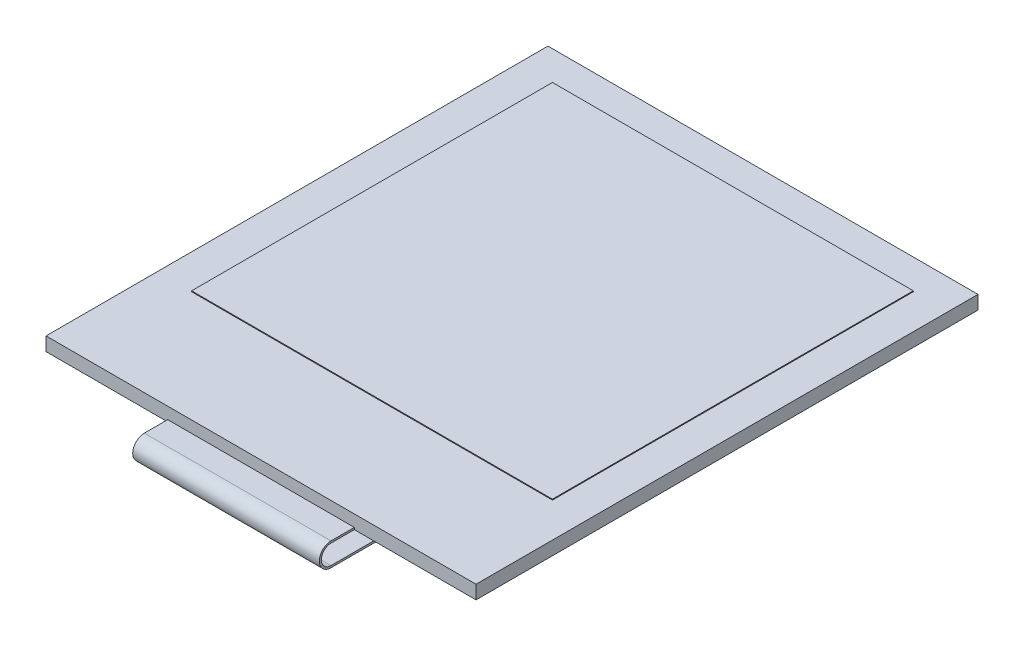
SolidWorks part; units mm, degrees
ref_plane "前视基准面" through (0, 0, 0) normal (0, 0, 1) x (1, 0, 0)
ref_plane "上视基准面" through (0, 0, 0) normal (0, 1, 0) x (1, 0, 0)
ref_plane "右视基准面" through (0, 0, 0) normal (1, 0, 0) x (0, 0, -1)
other "Configuration Table"
sketch "草图1" plane through (0, 0, 0) normal (0, 1, 0) x (1, 0, 0)
  line L1 (-9.28, -9.28) -> (9.28, -9.28)
  line L2 (-9.28, -9.28) -> (-9.28, 9.28)
  line L3 (-9.28, 9.28) -> (9.28, 9.28)
  line L4 (9.28, -9.28) -> (9.28, 9.28)
  line L5 (-9.28, -9.28) -> (9.28, 9.28) construction
  line L6 (-9.28, 9.28) -> (9.28, -9.28) construction
  line L7 (-11.06, 10.83) -> (11.06, 10.83)
  line L8 (-11.06, 10.83) -> (-11.06, -14.99)
  line L9 (-11.06, -14.99) -> (11.06, -14.99)
  line L10 (11.06, 10.83) -> (11.06, -14.99)
  point P0 (0, 0)
  dimension "D1" = 18.56
  dimension "D2" = 22.12
  dimension "D3" = 25.82
  dimension "D4" = 11.06
  dimension "D5" = 14.99
extrude "凸台-拉伸1" add sketch "草图1" along normal blind 0.7
extrude "凸台-拉伸2" add sketch "草图1<2>" along normal blind 0.745 contours L1 L4 L3 L2 region at (0, 0, 0)
sketch "草图1<2>" plane through (0, 0, 0) normal (0, 1, 0) x (1, 0, 0) same geometry as "草图1"
sketch "草图2" plane through (0, 0, 0) normal (1, 0, 0) x (0, 0, -1)
  line L0 (-14.99, 0) -> (-16.19, 0)
  line L1 (-16.19, -1) -> (-12.76, -1)
  line L2 (-16.19, 0) -> (-16.19, -1) construction
  line L3 (-14.99, 0.1) -> (-16.19, 0.1)
  line L4 (-16.19, -1.1) -> (-12.76, -1.1)
  line L5 (-14.99, 0) -> (-14.99, 0.1)
  line L6 (-12.76, -1) -> (-12.76, -1.1)
  arc A0 (-16.19, 0) -> (-16.19, -1) centre (-16.19, -0.5) ccw
  arc A1 (-16.19, 0.1) -> (-16.19, -1.1) centre (-16.19, -0.5) ccw
  dimension "D1" = 0.5
  dimension "D2" = 1.2
  dimension "D3" = 3.43
  dimension "D4" = 0.1
extrude "凸台-拉伸3" add sketch "草图2" along normal blind 4.8 and the other way blind 4.8
sketch "草图3" plane through (0, -1.1, 0) normal (0, -1, 0) x (1, 0, 0)
  line L0 (-4.8, 12.76) -> (4.8, 12.76) construction
  line L1 (-2.75, 12.76) -> (2.75, 12.76)
  line L2 (-2.75, 12.76) -> (-2.75, 4.76)
  line L3 (-2.75, 4.76) -> (2.75, 4.76)
  line L4 (2.75, 12.76) -> (2.75, 4.76)
  line L5 (0, 15.1973) -> (0, -3.5383) construction
  dimension "D1" = 8
  dimension "D2" = 5.5
extrude "凸台-拉伸4" add sketch "草图3" against normal blind 0.1
sketch "草图4" plane through (0, -1.1, 0) normal (0, -1, 0) x (1, 0, 0)
  line L0 (2.75, 4.76) -> (2.75, 12.76) construction
  line L1 (-2.75, 4.76) -> (2.75, 4.76)
  line L2 (-2.75, 4.76) -> (-2.75, 9.26)
  line L3 (-2.75, 9.26) -> (2.75, 9.26)
  line L4 (2.75, 4.76) -> (2.75, 9.26)
  dimension "D1" = 4.5
extrude "凸台-拉伸5" add sketch "草图4" along normal blind 0.2
